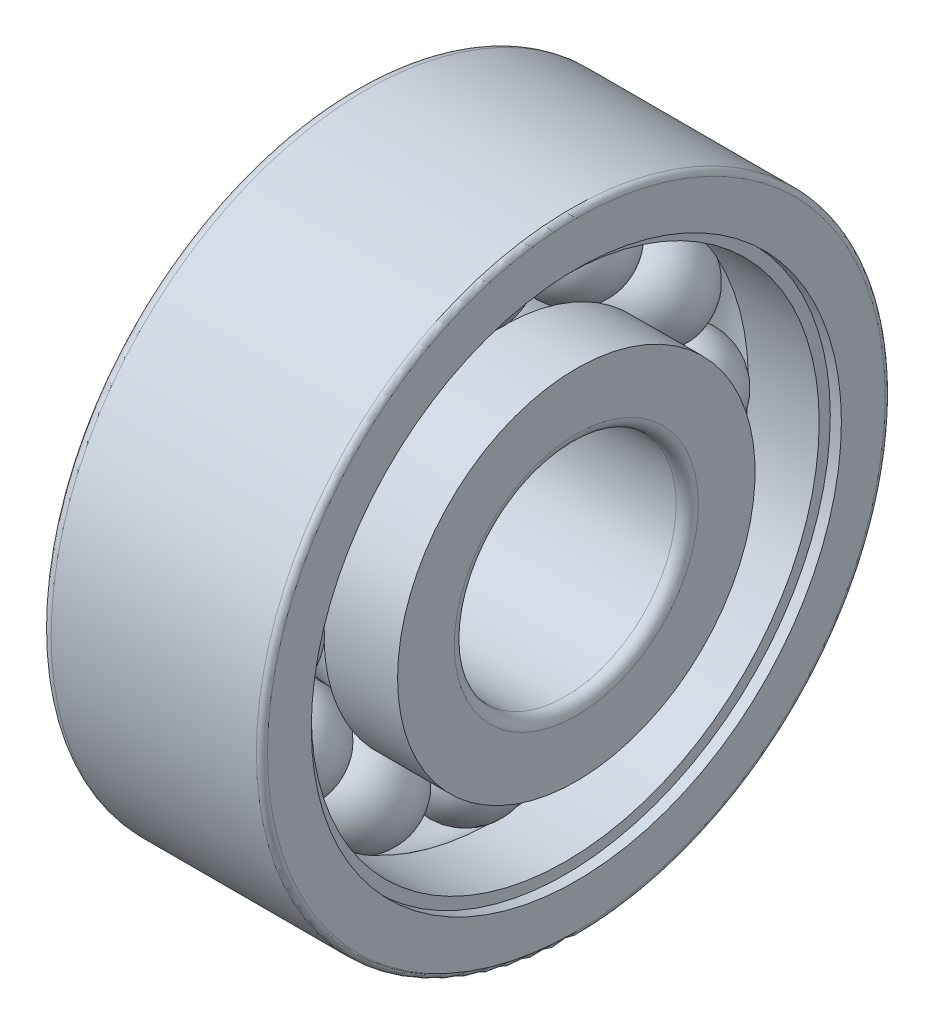
SolidWorks part; units mm, degrees
ref_plane "Front" through (0, 0, 0) normal (0, 0, 1) x (1, 0, 0)
ref_plane "Top" through (0, 0, 0) normal (0, 1, 0) x (1, 0, 0)
ref_plane "Right" through (0, 0, 0) normal (1, 0, 0) x (0, 0, -1)
sketch "Sketch1" plane through (0, 0, 0) normal (0, 0, 1) x (1, 0, 0)
  line L0 (-3.0919, 0) -> (2.899, 0) construction
  line L1 (-3.0919, 5.75) -> (2.899, 5.75) construction
  line L2 (-1.375, 5.75) -> (1.375, 5.75)
  arc A0 (-1.375, 5.75) -> (1.375, 5.75) centre (0, 5.75) ccw
  dimension "R" = 1.375
  dimension "D1" = 5.75
revolve "Revolve1" add sketch "Sketch1" angle 360 about L1
sketch "Sketch2" plane through (0, 0, 0) normal (0, 0, 1) x (1, 0, 0)
  line L0 (-3, 4.8333) -> (-1.0114, 4.8333)
  line L1 (3, 4.8333) -> (3, 3)
  line L2 (3, 3) -> (-3, 3)
  line L3 (-3, 3) -> (-3, 4.8333)
  line L4 (-2.9924, 0) -> (3.9982, 0) construction
  line L5 (-1.8743, 5.75) -> (3.1755, 5.75) construction
  line L7 (1.0114, 4.8333) -> (3, 4.8333)
  line L8 (-3, 6.2861) -> (-3, 1.454) construction
  arc A0 (-1.0114, 4.8333) -> (1.0114, 4.8333) centre (0, 5.75) ccw
  dimension "D2" = 1.365
  dimension "D1" = 5.75
  dimension "d" = 6
  dimension "D3" = 9.6667
  dimension "T" = 6
  dimension "D6" = 3
  dimension "B" = 6
revolve "Revolve2" add sketch "Sketch2" angle 360 about L4
sketch "Sketch3" plane through (0, 0, 0) normal (0, 0, 1) x (1, 0, 0)
  line L0 (-3, 6.6667) -> (-3, 8.5)
  line L1 (-3, 8.5) -> (3, 8.5)
  line L2 (3, 8.5) -> (3, 7.1667)
  line L3 (2.7, 6.8667) -> (0.785, 6.8667)
  line L4 (-2.9924, 0) -> (3.4329, 0) construction
  line L6 (-1.7375, 5.75) -> (2.2712, 5.75) construction
  line L7 (-1.0114, 6.6667) -> (-3, 6.6667)
  line L8 (2.7, 6.8667) -> (2.7, 7.1667)
  line L9 (2.7, 7.1667) -> (3, 7.1667)
  arc A0 (0.785, 6.8667) -> (-1.0114, 6.6667) centre (0, 5.75) ccw
  dimension "D4" = 1.365
  dimension "D1" = 5.75
  dimension "D2" = 3
  dimension "B" = 6
  dimension "D3" = 13.7333
  dimension "DD" = 17
  dimension "D5" = 13.3333
  dimension "D6" = 0.3
  dimension "D7" = 0.3
revolve "Revolve3" add sketch "Sketch3" angle 360 about L4
pattern_circular "Circular-Pattern1" count 12 over 360 about axis through (-2.9924, 0, 0) along (1, 0, 0) of "Revolve1"
fillet "Fillet1" radius 0.3 2 edges at (3, 0, 3) (-3, 0, 8.5)
fillet "Fillet2" radius 0.15 2 edges at (3, 0, 8.5) (-3, 0, 3)
equation "\"R@Sketch1\" =  ( \"DD@Sketch3\" - \"d@Sketch2\" )  / 8"
equation "\"D1@Sketch1\"=(\"d@Sketch2\"+\"DD@Sketch3\")/4"
equation "\"D1@Sketch2\"=(\"d@Sketch2\"+\"DD@Sketch3\")/4"
equation "\"D3@Sketch2\" =  \"d@Sketch2\"+  ( \"DD@Sketch3\" - \"d@Sketch2\" )  /3"
equation "\"D2@Sketch2\" =  ( \"DD@Sketch3\" - \"d@Sketch2\" )  / 8 - 0.01"
equation "\"D6@Sketch2\" = \"B@Sketch2\" / 2"
equation "\"B@Sketch3\" = \"B@Sketch2\""
equation "\"D2@Sketch3\" = \"B@Sketch3\" / 2"
equation "\"D1@Sketch3\"=(\"d@Sketch2\"+\"DD@Sketch3\")/4"
equation "\"D3@Sketch3\" = (  \"DD@Sketch3\" -  (\"DD@Sketch3\" - \"d@Sketch2\"  )  / 3 )  * 1.03"
equation "\"D5@Sketch3\" = \"DD@Sketch3\" -  (  \"DD@Sketch3\" - \"d@Sketch2\")  / 3"
equation "\"D6@Sketch3\" = \"d@Sketch2\" / 20"
equation "\"D7@Sketch3\"=\"D6@Sketch3\""
equation "\"D4@Sketch3\"=(\"DD@Sketch3\"-\"d@Sketch2\")/8-0.01"
equation "\"m@Circular-Pattern1\" = int( 3.14159265 / atn(\"R@Sketch1\" / sqr((\"d@Sketch2\"+\"DD@Sketch3\")/4 * (\"d@Sketch2\"+\"DD@Sketch3\")/4 - \"R@Sketch1\" *  \"R@Sketch1\")))-1"
